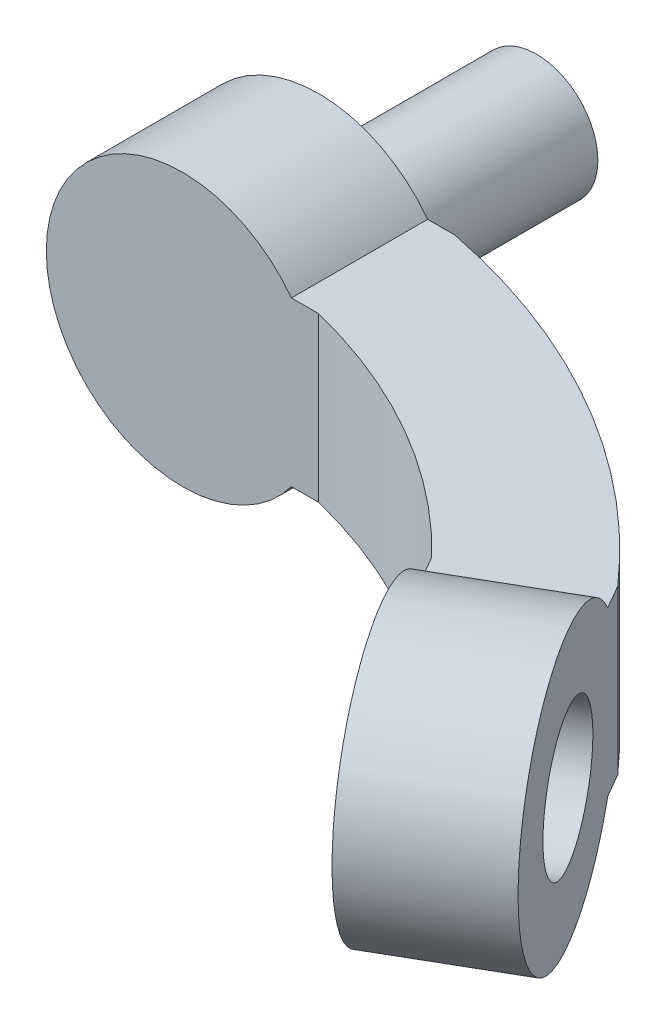
SolidWorks part; units mm, degrees
ref_plane "前视基准面" through (0, 0, 0) normal (0, 0, 1) x (1, 0, 0)
ref_plane "上视基准面" through (0, 0, 0) normal (0, 1, 0) x (1, 0, 0)
ref_plane "右视基准面" through (0, 0, 0) normal (1, 0, 0) x (0, 0, -1)
other "Configuration Table"
sketch "草图2" plane through (0, 0, 0) normal (0, 0, 1) x (1, 0, 0)
  circle A0 centre (0, 0) radius 5
  dimension "D1" = 10
extrude "凸台-拉伸3" add sketch "草图2" along normal blind 5
sketch "草图3" plane through (0, 0, 0) normal (0, 1, 0) x (1, 0, 0)
  line L0 (0, 0) -> (0, -25) construction
  line L1 (0, -25) -> (20.1468, -13.3682) construction
  line L2 (14.8205, -10.6699) -> (19.1506, -8.1699)
  line L3 (0, 0) -> (5, 0)
  line L4 (0, 0) -> (0, -5)
  line L5 (0, -5) -> (5, -5)
  line L6 (5, 0) -> (5, -5)
  line L15 (19.1506, -8.1699) -> (21.6506, -12.5)
  line L16 (21.6506, -12.5) -> (17.3205, -15)
  line L17 (17.3205, -15) -> (14.8205, -10.6699)
  arc A0 (5, -5) -> (14.8205, -10.6699) centre (0, -25) cw
  arc A1 (5, 0) -> (19.1506, -8.1699) centre (0, -25) cw
  dimension "D4" = 20
  dimension "D1" = 60
  dimension "D2" = 5
  dimension "D3" = 5
  dimension "D5" = 5
extrude "凸台-拉伸4" add sketch "草图3" along normal blind 3 and the other way blind 3 separate body contours A1 L6 A0 L2 region at (11.421, 0, 5.2182)
revolve "旋转1" add sketch "草图3<3>" angle 360 about L1 region at (18.2356, 0, 11.5849)
sketch "草图3<3>" plane through (0, 0, 0) normal (0, 1, 0) x (1, 0, 0) same geometry as "草图3"
sketch "草图4" plane through (8.3253, 0, 14.4199) normal (0.5, 0, 0.866) x (0.866, 0, -0.5)
  line L4 (12.5, 3) -> (7.5, 3)
  line L5 (7.5, 3) -> (7.5, -3)
  line L6 (7.5, -3) -> (12.5, -3)
  line L7 (12.5, -3) -> (12.5, 3)
  line L8 (12.5, 3) -> (7.5, 3)
  line L9 (7.5, 3) -> (7.5, -3)
  line L10 (7.5, -3) -> (12.5, -3)
  line L11 (12.5, -3) -> (12.5, 3)
  dimension "D1" = 0
extrude "凸台-拉伸5" add sketch "草图4" along normal blind 3
sketch "草图5" plane through (5, 0, 0) normal (-1, 0, 0) x (0, 0, 1)
  line L4 (5, -3) -> (5, 3)
  line L5 (5, 3) -> (0, 3)
  line L6 (0, 3) -> (0, -3)
  line L7 (0, -3) -> (5, -3)
  line L8 (5, -3) -> (5, 3)
  line L9 (5, 3) -> (0, 3)
  line L10 (0, 3) -> (0, -3)
  line L11 (0, -3) -> (5, -3)
  dimension "D1" = 0
extrude "凸台-拉伸6" add sketch "草图5" along normal blind 3
sketch "草图6" plane through (6.4952, 0, -3.75) normal (-0.866, 0, 0.5) x (0.5, 0, 0.866)
  circle A0 centre (21.6506, 0) radius 2.5
  dimension "D1" = 5
extrude "切除-拉伸1" cut sketch "草图6" against normal blind 5
sketch "草图7" plane through (0, 0, 5) normal (0, 0, 1) x (1, 0, 0)
  circle A0 centre (0, 0) radius 2.25
  dimension "D1" = 4.5
extrude "凸台-拉伸7" add sketch "草图7" against normal blind 8 from surface starting at face at (2.25, 0, 0)
